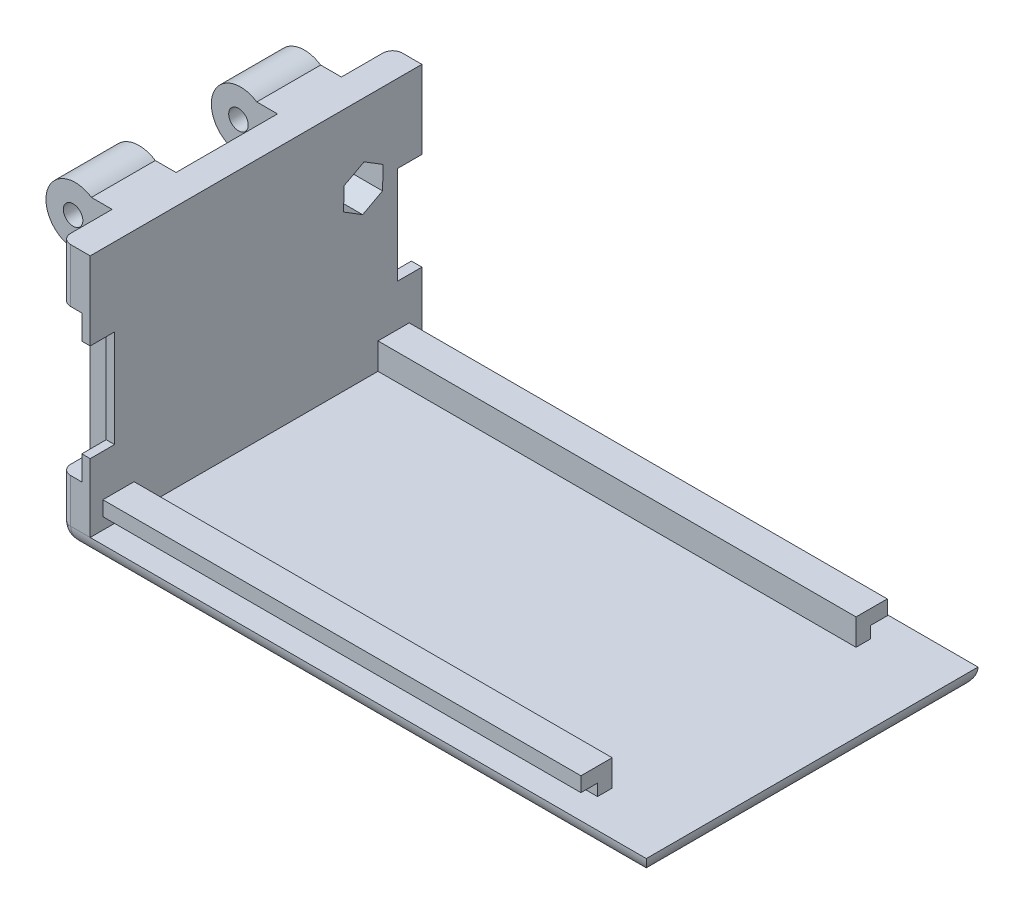
SolidWorks part; units mm, degrees
ref_plane "Front Plane" through (0, 0, 0) normal (0, 0, 1) x (1, 0, 0)
ref_plane "Top Plane" through (0, 0, 0) normal (0, 1, 0) x (1, 0, 0)
ref_plane "Right Plane" through (0, 0, 0) normal (1, 0, 0) x (0, 0, -1)
sketch "Sketch1" plane through (0, 0, 0) normal (0, 1, 0) x (1, 0, 0)
  line L1 (0, 0) -> (60, 0)
  line L2 (0, 0) -> (0, 34)
  line L3 (0, 34) -> (60, 34)
  line L4 (60, 0) -> (60, 34)
  line L5 (0, 0) -> (60, 34) construction
  line L6 (0, 34) -> (60, 0) construction
  point P4 (30, 17)
  dimension "D1" = 34
  dimension "D2" = 60
extrude "Boss-Extrude1" add sketch "Sketch1" along normal blind 2
sketch "Sketch2" plane through (0, 2, 0) normal (0, 1, 0) x (1, 0, 0)
  line L0 (60, 34) -> (0, 34) construction
  line L1 (0, 0) -> (3, 0)
  line L2 (0, 0) -> (0, 34)
  line L3 (0, 34) -> (3, 34)
  line L4 (3, 0) -> (3, 34)
  line L5 (0, 0) -> (3, 34) construction
  line L6 (0, 34) -> (3, 0) construction
  point P4 (1.5, 17)
  dimension "D1" = 3
extrude "Boss-Extrude2" add sketch "Sketch2" along normal blind 25 contours L4 L3 L2 L1
sketch "Sketch3" plane through (3, 0, 0) normal (1, 0, 0) x (0, 0, -1)
  line L0 (0, 2) -> (34, 2) construction
  line L1 (4.5, 2) -> (3, 2)
  line L2 (4.5, 2) -> (4.5, 4.7)
  line L3 (4.5, 4.7) -> (3, 4.7)
  line L4 (3, 2) -> (3, 4.7)
  line L5 (4.5, 2) -> (3, 4.7) construction
  line L6 (4.5, 4.7) -> (3, 2) construction
  line L7 (0, 27) -> (0, 2) construction
  line L8 (3, 4.7) -> (1.3, 4.7)
  line L9 (3, 4.7) -> (3, 3.2)
  line L10 (3, 3.2) -> (1.3, 3.2)
  line L11 (1.3, 4.7) -> (1.3, 3.2)
  line L12 (3, 4.7) -> (1.3, 3.2) construction
  line L13 (3, 3.2) -> (1.3, 4.7) construction
  line L14 (17, 2) -> (17, 9.9529) construction
  line L15 (31, 3.2) -> (32.7, 3.2)
  line L16 (32.7, 4.7) -> (32.7, 3.2)
  line L17 (31, 4.7) -> (32.7, 4.7)
  line L18 (31, 4.7) -> (31, 3.2)
  line L19 (29.5, 4.7) -> (31, 4.7)
  line L20 (31, 2) -> (31, 4.7)
  line L21 (29.5, 2) -> (31, 2)
  line L22 (29.5, 2) -> (29.5, 4.7)
  point P4 (3.75, 3.35)
  point P10 (2.15, 3.95)
  dimension "D1" = 1.5
  dimension "D2" = 2.7
  dimension "D3" = 1.5
  dimension "D4" = 3
  dimension "D5" = 1.7
extrude "Boss-Extrude3" add sketch "Sketch3" along normal blind 49 contours L17 L18 L15 L16 | L4 L1 L2 L3 | L8 L11 L10 L9 | L20 L21 L22 L19 region at (3, 3.95, -31.85)
sketch "Sketch4" plane through (0, 0, 0) normal (0, 0, 1) x (1, 0, 0)
  line L0 (0, 27) -> (0, 0) construction
  line L1 (3, 27) -> (0, 27)
  line L2 (3, 27) -> (3, 22)
  line L3 (3, 22) -> (0, 22)
  line L5 (3, 27) -> (-5, 22) construction
  line L6 (3, 22) -> (-5, 27) construction
  line L8 (0, 22) -> (-2.1254, 22)
  line L9 (0, 27) -> (-2.1254, 27)
  line L10 (0, 22) -> (0, 27)
  circle A1 centre (-3.7837, 24.5) radius 3
  point P4 (-1, 24.5)
  line M12 (0, 27) -> (0, 0)
  dimension "D3" = 6
  dimension "D1" = 8
  dimension "D2" = 5
extrude "Boss-Extrude4" add sketch "Sketch4" against normal blind 30 contours M12 | A1 region at (-0.6518, 24.5, 0)
sketch "Sketch5" plane through (0, 0, 0) normal (0, -1, 0) x (1, 0, 0)
  line L0 (0, -34) -> (0, 0) construction
  line L1 (0, 0) -> (-8, 0)
  line L2 (0, 0) -> (0, -5.25)
  line L3 (0, -5.25) -> (-8, -5.25)
  line L4 (-8, 0) -> (-8, -5.25)
  line L5 (0, 0) -> (-8, -5.25) construction
  line L6 (0, -5.25) -> (-8, 0) construction
  line L7 (60, -34) -> (0, -34) construction
  line L8 (0, -28.75) -> (-8, -28.75)
  line L9 (0, -28.75) -> (0, -34)
  line L10 (0, -34) -> (-8, -34)
  line L11 (-8, -28.75) -> (-8, -34)
  line L12 (0, -28.75) -> (-8, -34) construction
  line L13 (0, -34) -> (-8, -28.75) construction
  line L14 (0, 0) -> (60, 0) construction
  line L16 (0, -11.8) -> (-8, -11.8)
  line L17 (0, -11.8) -> (0, -22.2)
  line L18 (0, -22.2) -> (-8, -22.2)
  line L19 (-8, -11.8) -> (-8, -22.2)
  line L20 (0, -11.8) -> (-8, -22.2) construction
  line L21 (0, -22.2) -> (-8, -11.8) construction
  point P4 (-4, -2.625)
  point P11 (-4, -31.375)
  point P20 (-4, -17)
  line M5 (0, 0) -> (0, -34)
  dimension "D1" = 5.25
  dimension "D2" = 5.25
  dimension "D3" = 0
  dimension "D4" = 0
  dimension "D5" = 8
  dimension "D6" = 8
  dimension "D7" = 11.8
  dimension "D8" = 11.8
extrude "Cut-Extrude1" cut sketch "Sketch5" against normal blind 30 contours L16 L19 L18 M5 | L3 L4 L1 L2 | L8 L11 L10 L9 region at (-4, 0, -17)
sketch "Sketch6" plane through (0, 0, 0) normal (0, 0, 1) x (1, 0, 0)
  line L1 (0, 27) -> (0, 0) construction
  circle A0 centre (-4, 24.5) radius 1
  dimension "D1" = 2
  dimension "D2" = 4
extrude "Cut-Extrude2" cut sketch "Sketch6" against normal blind 28
sketch "Sketch7" plane through (0, 0, 0) normal (-1, 0, 0) x (0, 0, 1)
  line L0 (0, 27) -> (0, 0) construction
  line L1 (-30.0352, 20.0914) -> (-29.9628, 17.7832)
  line L2 (-29.9628, 17.7832) -> (-27.9276, 16.6917)
  line L3 (-27.9276, 16.6917) -> (-25.9648, 17.9086)
  line L4 (-25.9648, 17.9086) -> (-26.0372, 20.2168)
  line L5 (-26.0372, 20.2168) -> (-28.0724, 21.3083)
  line L6 (-28.0724, 21.3083) -> (-30.0352, 20.0914)
  line L7 (0, 27) -> (-5.25, 27) construction
  circle A0 centre (-28, 19) radius 2 construction
  dimension "D1" = 4
  dimension "D2" = 28
  dimension "D3" = 8
extrude "Cut-Extrude3" cut sketch "Sketch7" against normal blind 28
fillet "Fillet1" radius 2 4 edges at (30, 0, 0) (60, 0, -17) (30, 0, -34) (0, 0, -17)
fillet "Fillet3" radius 1 4 edges at (0.5858, 0.5858, -33.4142) (0.5858, 0.5858, -0.5858) (0, 14.5, -34) (0, 14.5, 0)
sketch "Sketch8" plane through (0, 0, -34) normal (0, 0, -1) x (-1, 0, 0)
  line L0 (-1, 27) -> (-3, 27) construction
  line L1 (0.0743, 6.5) -> (-1.9257, 6.5)
  line L2 (0.0743, 6.5) -> (0.0743, 21.5)
  line L3 (0.0743, 21.5) -> (-1.9257, 21.5)
  line L4 (-1.9257, 6.5) -> (-1.9257, 21.5)
  line L5 (0.0743, 6.5) -> (-1.9257, 21.5) construction
  line L6 (0.0743, 21.5) -> (-1.9257, 6.5) construction
  point P4 (-0.9257, 14)
  dimension "D1" = 5.5
  dimension "D2" = 15
  dimension "D3" = 2
extrude "Cut-Extrude4" cut sketch "Sketch8" against normal blind 3 contours L2 L3 L4 L1
sketch "Sketch9" plane through (1.9257, 0, 0) normal (-1, 0, 0) x (0, 0, 1)
  line L0 (-34, 6.5) -> (-34, 21.5) construction
  line L1 (-34, 9) -> (-31.5, 9)
  line L2 (-34, 9) -> (-34, 19)
  line L3 (-34, 19) -> (-31.5, 19)
  line L4 (-31.5, 9) -> (-31.5, 19)
  line L5 (-34, 9) -> (-31.5, 19) construction
  line L6 (-34, 19) -> (-31.5, 9) construction
  line L7 (-31, 21.5) -> (-34, 21.5) construction
  point P4 (-32.75, 14)
  dimension "D1" = 10
  dimension "D2" = 2.5
  dimension "D3" = 2.5
extrude "Cut-Extrude5" cut sketch "Sketch9" against normal blind 3 contours L1 L4 L3 L2
sketch "Sketch11" plane through (0, 0, 0) normal (0, 0, 1) x (1, 0, 0)
  line L0 (1, 27) -> (3, 27) construction
  line L1 (2.1464, 21.5) -> (0, 21.5)
  line L2 (2.1464, 21.5) -> (2.1464, 6.5)
  line L3 (2.1464, 6.5) -> (0, 6.5)
  line L4 (0, 21.5) -> (0, 6.5)
  line L5 (2.1464, 21.5) -> (0, 6.5) construction
  line L6 (2.1464, 6.5) -> (0, 21.5) construction
  point P4 (1.0732, 14)
  dimension "D1" = 15
  dimension "D2" = 5.5
extrude "Cut-Extrude6" cut sketch "Sketch11" against normal blind 3
sketch "Sketch12" plane through (2.1464, 0, 0) normal (-1, 0, 0) x (0, 0, 1)
  line L0 (0, 6.5) -> (0, 21.5) construction
  line L1 (0, 9) -> (-2.5, 9)
  line L2 (0, 9) -> (0, 19)
  line L3 (0, 19) -> (-2.5, 19)
  line L4 (-2.5, 9) -> (-2.5, 19)
  line L5 (0, 9) -> (-2.5, 19) construction
  line L6 (0, 19) -> (-2.5, 9) construction
  line L7 (0, 6.5) -> (-1, 6.5) construction
  point P4 (-1.25, 14)
  dimension "D1" = 10
  dimension "D2" = 2.5
  dimension "D3" = 2.5
extrude "Cut-Extrude7" cut sketch "Sketch12" against normal blind 3
sketch "Sketch13" plane through (0, 0, 0) normal (0, -1, 0) x (-1, 0, 0)
  line L0 (-58, 12) -> (-2, 12) construction
  line L1 (-58, 32) -> (-58, 2) construction
  line L2 (-2, 2) -> (-2, 32) construction
  line L3 (-58, 2) -> (-2, 2) construction
  text T0 "FLEXI" font "Century Gothic" height in points 45
  dimension "D1" = 10
extrude "Cut-Extrude8" cut sketch "Sketch13" against normal blind 1.2
